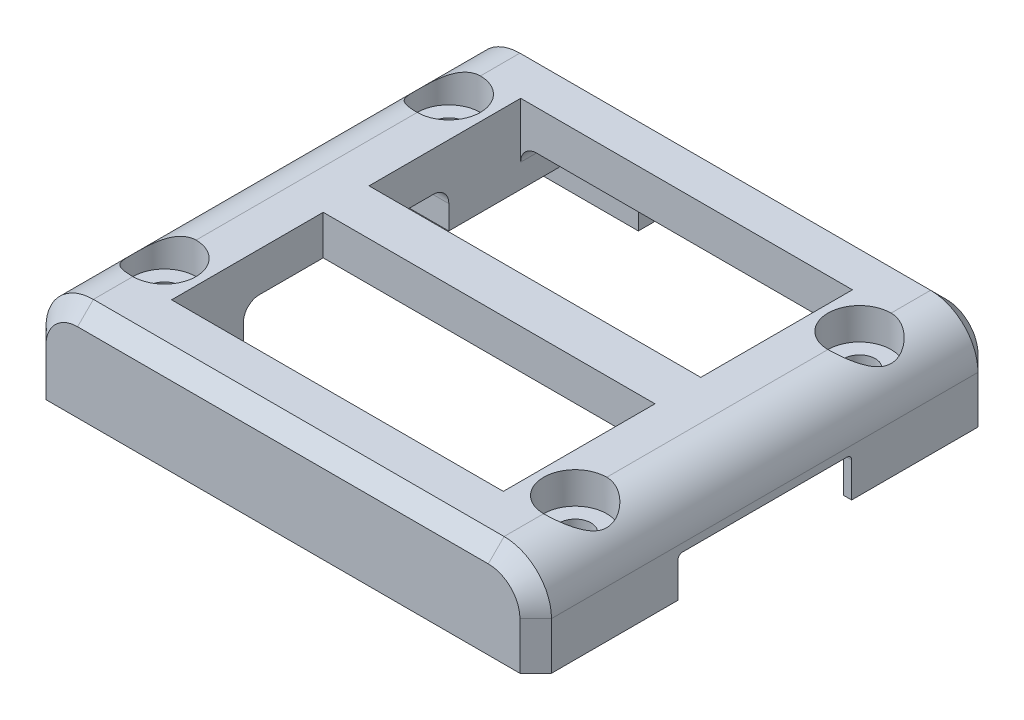
SolidWorks part; units mm, degrees
ref_plane "Front Plane" through (0, 0, 0) normal (0, 0, 1) x (1, 0, 0)
ref_plane "Top Plane" through (0, 0, 0) normal (0, 1, 0) x (1, 0, 0)
ref_plane "Right Plane" through (0, 0, 0) normal (1, 0, 0) x (0, 0, -1)
sketch "Sketch1" plane through (0, 0, 0) normal (0, 1, 0) x (1, 0, 0)
  line L0 (-16, -14.5) -> (16, -14.5)
  line L1 (-16, -14.5) -> (-16, 14.5)
  line L2 (16, -14.5) -> (16, 14.5)
  line L3 (-16, 14.5) -> (16, 14.5)
  line L4 (-16, -14.5) -> (16, 14.5) construction
  line L5 (16, -14.5) -> (-16, 14.5) construction
  point P1 (0, 0)
  dimension "D1" = 32
  dimension "D2" = 29
extrude "Boss-Extrude1" add sketch "Sketch1" along normal blind 6 contours L3 L2 L0 L1
sketch "Sketch2" plane through (0, 6, 0) normal (0, 1, 0) x (1, 0, 0)
  line L0 (-13, -9) -> (13, -9) construction
  line L1 (-13, -9) -> (-13, 9) construction
  line L2 (13, -9) -> (13, 9) construction
  line L3 (-13, 9) -> (13, 9) construction
  line L4 (-13, -9) -> (13, 9) construction
  line L5 (13, -9) -> (-13, 9) construction
  circle A0 centre (-13, 9) radius 1
  circle A1 centre (13, 9) radius 1
  circle A2 centre (13, -9) radius 1
  circle A3 centre (-13, -9) radius 1
  point P1 (0, 0)
  dimension "D1" = 2
  dimension "D2" = 26
  dimension "D3" = 18
extrude "Cut-Extrude1" cut sketch "Sketch2" against normal blind 10
sketch "Sketch3" plane through (0, 6, 0) normal (0, 1, 0) x (1, 0, 0)
  line L0 (0, -6.25) -> (0, 6.25) construction
  line L1 (-10.5, 1.45) -> (10.5, 1.45)
  line L2 (-10.5, 1.45) -> (-10.5, 11.05)
  line L3 (10.5, 1.45) -> (10.5, 11.05)
  line L4 (-10.5, 11.05) -> (10.5, 11.05)
  line L5 (-10.5, 1.45) -> (10.5, 11.05) construction
  line L6 (10.5, 1.45) -> (-10.5, 11.05) construction
  line L7 (-10.5, -11.05) -> (10.5, -11.05)
  line L8 (-10.5, -11.05) -> (-10.5, -1.45)
  line L9 (10.5, -11.05) -> (10.5, -1.45)
  line L10 (-10.5, -1.45) -> (10.5, -1.45)
  line L11 (-10.5, -11.05) -> (10.5, -1.45) construction
  line L12 (10.5, -11.05) -> (-10.5, -1.45) construction
  point P4 (0, 0)
  dimension "D1" = 9.6
  dimension "D2" = 21
  dimension "D3" = 12.5
extrude "Cut-Extrude2" cut sketch "Sketch3" against normal blind 10
sketch "Sketch4" plane through (0, 0, 0) normal (0, -1, 0) x (1, 0, 0)
  line L0 (15.5, 13.5) -> (-15.5, 13.5)
  line L1 (15.5, 13.5) -> (15.5, -13.5)
  line L2 (-15.5, 13.5) -> (-15.5, -13.5)
  line L3 (15.5, -13.5) -> (-15.5, -13.5)
  line L4 (15.5, 13.5) -> (-15.5, -13.5) construction
  line L5 (-15.5, 13.5) -> (15.5, -13.5) construction
  line L6 (-16, -14.5) -> (16, -14.5) construction
  point P1 (0, 0)
  dimension "D1" = 31
  dimension "D2" = 1
extrude "Cut-Extrude3" cut sketch "Sketch4" against normal blind 1
fillet "Fillet2" radius 3 2 edges at (-16, 6, 0) (16, 6, 0)
sketch "Sketch5" plane through (0, 6, 0) normal (0, 1, 0) x (1, 0, 0)
  circle A0 centre (-13, 9) radius 2
  circle A1 centre (13, 9) radius 2
  circle A2 centre (13, -9) radius 2
  circle A3 centre (-13, -9) radius 2
  dimension "D1" = 4
extrude "Cut-Extrude4" cut sketch "Sketch5" against normal blind 2
chamfer "Chamfer2" distance 1 angle 45 10 edges at (-16, 1.5, 14.5) (-15.1213, 5.1213, 14.5) (0, 6, 14.5) (15.1213, 5.1213, 14.5) (16, 1.5, 14.5) (-16, 1.5, -14.5) (-15.1213, 5.1213, -14.5) (0, 6, -14.5) (15.1213, 5.1213, -14.5) (16, 1.5, -14.5)
sketch "Sketch6" plane through (0, 0, 0) normal (0, -1, 0) x (1, 0, 0)
  line L0 (-15.5, 13.5) -> (-15.5, -13.5) construction
  line L1 (-15, -5.5) -> (-16, -5.5)
  line L2 (-15, -5.5) -> (-15, 5.5)
  line L3 (-15, 5.5) -> (-16, 5.5)
  line L4 (-16, -5.5) -> (-16, 5.5)
  line L5 (-15, -5.5) -> (-16, 5.5) construction
  line L6 (-15, 5.5) -> (-16, -5.5) construction
  line L7 (-16, 13.5) -> (-16, -13.5) construction
  line L8 (15.5, -13.5) -> (15.5, 13.5) construction
  line L9 (15, -5.5) -> (16, -5.5)
  line L10 (15, -5.5) -> (15, 5.5)
  line L11 (15, 5.5) -> (16, 5.5)
  line L12 (16, -5.5) -> (16, 5.5)
  line L13 (15, -5.5) -> (16, 5.5) construction
  line L14 (15, 5.5) -> (16, -5.5) construction
  line L15 (16, 13.5) -> (16, -13.5) construction
  point P0 (-15.5, 0)
  point P9 (15.5, 0)
  dimension "D1" = 11
extrude "Cut-Extrude5" cut sketch "Sketch6" against normal blind 2.5
fillet "Fillet3" radius 0.3 4 edges at (15.5, 2.5, 5.5) (15.5, 2.5, -5.5) (-15.5, 2.5, -5.5) (-15.5, 2.5, 5.5)
sketch "Sketch7" plane through (0, 1, 0) normal (0, -1, 0) x (1, 0, 0)
  line L0 (-15.5, 13.5) -> (-15.5, 5.5) construction
  line L1 (15.5, -6.5) -> (-15.5, -6.5)
  line L2 (15.5, -6.5) -> (15.5, 6.5)
  line L3 (15.5, 6.5) -> (-15.5, 6.5)
  line L4 (-15.5, -6.5) -> (-15.5, 6.5)
  line L5 (15.5, -6.5) -> (-15.5, 6.5) construction
  line L6 (15.5, 6.5) -> (-15.5, -6.5) construction
  point P0 (0, 0)
  dimension "D1" = 13
extrude "Cut-Extrude6" cut sketch "Sketch7" against normal blind 2.5
fillet "Fillet4" radius 1 4 edges at (13, 3.5, -6.5) (13, 3.5, 6.5) (-13, 3.5, -6.5) (-13, 3.5, 6.5)
sketch "Эскиз1" plane through (0, 1, 0) normal (0, -1, 0) x (1, 0, 0)
  line L0 (-10.5, 1.45) -> (-10.5, 5.5) construction
  line L1 (-10.5, -1.45) -> (10.5, -1.45)
  line L2 (-10.5, -1.45) -> (-10.5, -13.5)
  line L3 (-10.5, -13.5) -> (10.5, -13.5)
  line L4 (10.5, -1.45) -> (10.5, -13.5)
  line L5 (-10.5, -1.45) -> (10.5, -13.5) construction
  line L6 (-10.5, -13.5) -> (10.5, -1.45) construction
  line L7 (10.5, 5.5) -> (10.5, 1.45) construction
  line L8 (-15.5, -13.5) -> (15.5, -13.5) construction
  line L9 (0, 0) -> (5.1222, 0) construction
  line L10 (10.5, 1.45) -> (-10.5, 1.45) construction
  point P0 (0, -7.475)
extrude "Вырез-Вытянуть1" cut sketch "Эскиз1" against normal up to surface (2.5 mm away) up to face at (0, 3.5, 0)
fillet "Скругление1" radius 1 2 edges at (10.5, 3.5, -12.275) (-10.5, 3.5, -12.275)
sketch "Эскиз2" plane through (0, 0, -13.5) normal (0, 0, 1) x (1, 0, 0)
  line L0 (-15, 0) -> (15, 0) construction
  line L1 (-5.5, 2.5) -> (5.5, 2.5)
  line L2 (-5.5, 2.5) -> (-5.5, 0)
  line L3 (-5.5, 0) -> (5.5, 0)
  line L4 (5.5, 2.5) -> (5.5, 0)
  line L5 (-5.5, 2.5) -> (5.5, 0) construction
  line L6 (-5.5, 0) -> (5.5, 2.5) construction
  line L7 (0, 0) -> (0, 5) construction
  line L8 (13, 5) -> (-13, 5) construction
  point P0 (0, 1.25)
  dimension "D1" = 11
  dimension "D2" = 2.5
extrude "Вырез-Вытянуть2" cut sketch "Эскиз2" against normal through all
fillet "Скругление2" radius 0.3 2 edges at (-5.5, 2.5, -14) (5.5, 2.5, -14)
equation "\"motor_diameter\"= 30"
equation "\"mm_diameter\"= IIF ( \"motor_diameter\" < 34 , 41 , \"motor_diameter\" + 8 )"
equation "\"upper_shafts_diameter\"= 5"
equation "\"upper_shats_length\"= 180"
equation "\"upper_bearing_d1\"= 10"
equation "\"upper_bearing_d2\"= 5"
equation "\"upper_bearing_h\"= 15"
equation "\"lower_shafts_diameter\"= 5"
equation "\"lower_shafts_length\"= 180"
equation "\"lower_bearing_d1\"= 10"
equation "\"lower_bearing_d2\"= 5"
equation "\"lower_bearing_h\"= 15"
equation "\"print_offset\"= 0.5"
equation "\"bh_screws_d\"= 2"
equation "\"bh_screws_h\"= 20"
equation "\"bh_screws_hh_d\"= 3.4"
equation "\"bh_screws_hh_h\"= 2"
equation "\"bh_nut_d\"= 3.8"
equation "\"bh_nut_h\"= 2"
equation "\"motor_screws_d\"= 3"
equation "\"motor_screws_h\"= 16"
equation "\"motor_screws_hh_d\"= 5.5"
equation "\"motor_screws_hh_h\"= 3"
equation "\"plate_hole_distance\"= 25.4"
equation "\"plate_screws_d\"= 6.5"
equation "\"shafts_diameter\"= IIF ( \"mm_diameter\" < 42 , 42 + 8 , \"mm_diameter\" + 8 )"
equation "\"central_hole_diameter\"= 8"
equation "\"bh_thikness\"= 4"
equation "\"D2@Sketch1\"=\"upper_bearing_h\"+\"bh_thikness\"*2+3*2"
